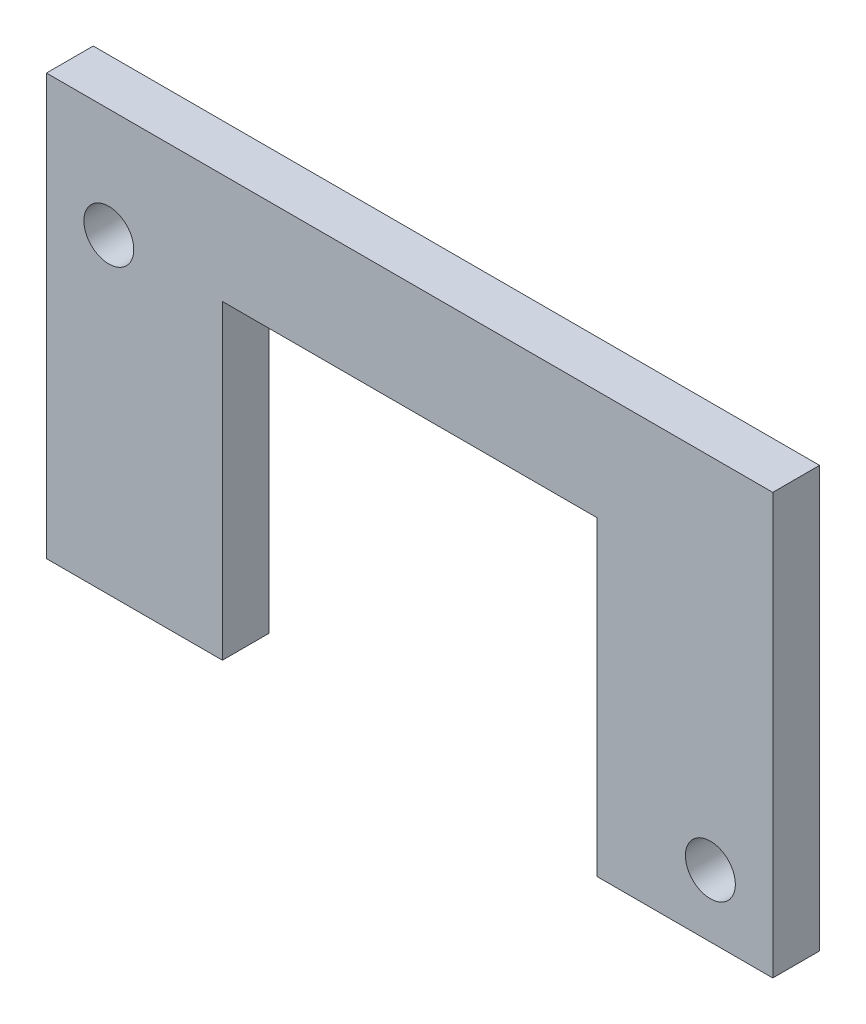
SolidWorks part; units mm, degrees
ref_plane "Front Plane" through (0, 0, 0) normal (0, 0, 1) x (1, 0, 0)
ref_plane "Top Plane" through (0, 0, 0) normal (0, 1, 0) x (1, 0, 0)
ref_plane "Right Plane" through (0, 0, 0) normal (1, 0, 0) x (0, 0, -1)
sketch "Sketch1" plane through (0, 0, 0) normal (0, 0, 1) x (1, 0, 0)
  line L1 (0, 0) -> (33.782, 0) construction
  line L2 (0, 0) -> (0, 19.812) construction
  line L3 (0, 19.812) -> (33.782, 19.812) construction
  line L4 (33.782, 0) -> (33.782, 19.812) construction
  line L5 (-1.5875, -1.5875) -> (35.3695, -1.5875)
  line L6 (-1.5875, -1.5875) -> (-1.5875, 19.812)
  line L7 (-1.5875, 19.812) -> (35.3695, 19.812)
  line L8 (35.3695, -1.5875) -> (35.3695, 19.812)
  circle A0 centre (1.5875, 14.2558) radius 1.27
  circle A1 centre (32.1945, 1.5875) radius 1.27
  dimension "D3" = 2.54
  dimension "D4" = 2.54
  dimension "D5" = 1.5875
  dimension "D6" = 1.5875
  dimension "D7" = 1.5875
  dimension "D8" = 5.5562
  dimension "D9" = 3.175
  dimension "D11" = 3.175
  dimension "D12" = 5.5562
  dimension "D1" = 19.812
  dimension "D2" = 33.782
  dimension "D10" = 3.175
extrude "Boss-Extrude1" add sketch "Sketch1" along normal blind 2.3813
sketch "Sketch2" plane through (0, 0, 2.3813) normal (0, 0, 1) x (1, 0, 0)
  line L5 (-1.5875, -1.5875) -> (35.3695, -1.5875) construction
  line L6 (7.366, -1.5875) -> (26.416, -1.5875)
  line L7 (7.366, -1.5875) -> (7.366, 14.224)
  line L8 (7.366, 14.224) -> (26.416, 14.224)
  line L9 (26.416, -1.5875) -> (26.416, 14.224)
  line L10 (-1.5875, -1.5875) -> (7.366, -1.5875) construction
  line L11 (26.416, -1.5875) -> (35.3695, -1.5875) construction
  line L12 (35.3695, 19.812) -> (-1.5875, 19.812) construction
  dimension "D1" = 19.05
  dimension "D2" = 5.588
extrude "Cut-Extrude1" cut sketch "Sketch2" against normal up to next
